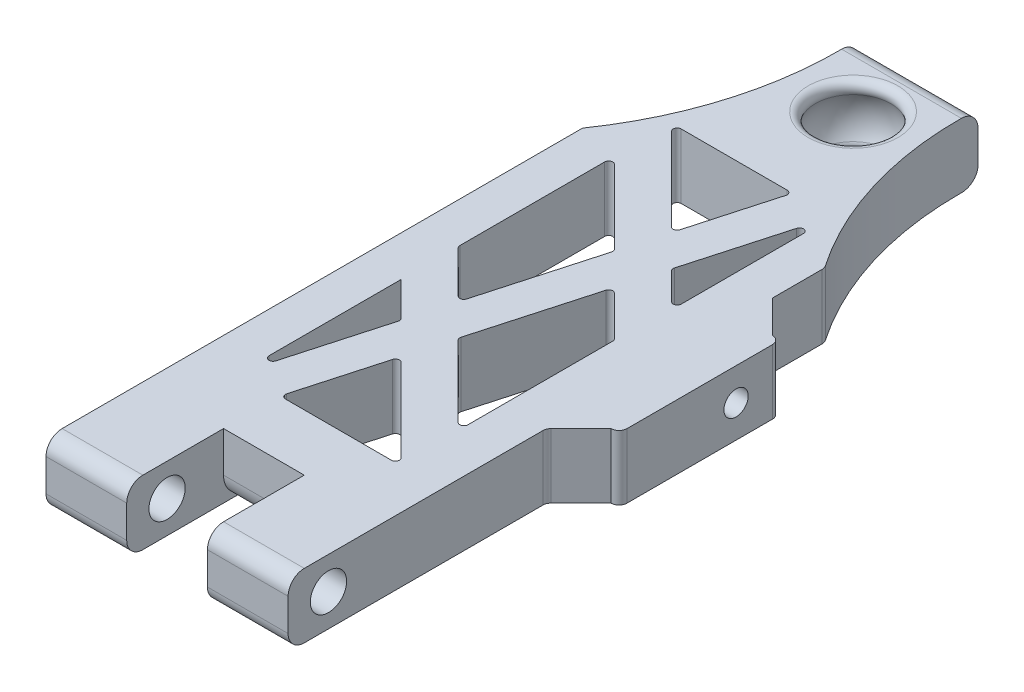
SolidWorks part; units mm, degrees
ref_plane "Front Plane" through (0, 0, 0) normal (0, 0, 1) x (1, 0, 0)
ref_plane "Top Plane" through (0, 0, 0) normal (0, 1, 0) x (1, 0, 0)
ref_plane "Right Plane" through (0, 0, 0) normal (1, 0, 0) x (0, 0, -1)
sketch "Sketch1" plane through (0, 0, 0) normal (0, 1, 0) x (1, 0, 0)
  line L1 (-15, 46.5) -> (15, 46.5)
  line L2 (-15, 46.5) -> (-15, -46.5)
  line L3 (-15, -46.5) -> (15, -46.5)
  line L4 (15, 46.5) -> (15, -46.5)
  line L5 (-15, 46.5) -> (15, -46.5) construction
  line L6 (-15, -46.5) -> (15, 46.5) construction
  point P0 (0, 0)
  dimension "D1" = 30
  dimension "D2" = 93
extrude "Boss-Extrude1" add sketch "Sketch1" along normal blind 8
sketch "Sketch2" plane through (0, 8, 0) normal (0, 1, 0) x (1, 0, 0)
  line L5 (-15, -46.5) -> (15, -46.5) construction
  line L6 (5, -46.5) -> (-5, -46.5)
  line L7 (5, -46.5) -> (5, -34.5)
  line L8 (5, -34.5) -> (-5, -34.5)
  line L9 (-5, -46.5) -> (-5, -34.5)
  line L10 (15, -46.5) -> (15, 46.5) construction
  dimension "D1" = 10
  dimension "D5" = 12
  dimension "D6" = 10
extrude "Cut-Extrude1" cut sketch "Sketch2" against normal blind 8
sketch "Sketch3" plane through (15, 0, 0) normal (1, 0, 0) x (0, 0, -1)
  line L0 (-46.5, 8) -> (-46.5, 0) construction
  line L1 (-46.5, 8) -> (46.5, 8) construction
  circle A0 centre (-41.5, 4) radius 2.25
  dimension "D1" = 4.5
  dimension "D2" = 5
  dimension "D3" = 4
extrude "Cut-Extrude2" cut sketch "Sketch3" against normal through all
fillet "Fillet1" radius 2 6 edges at (0, 0, -46.5) (0, 8, -46.5) (-10, 8, 46.5) (-10, 0, 46.5) (10, 0, 46.5) (10, 8, 46.5)
sketch "Sketch4" plane through (0, 8, 0) normal (0, 1, 0) x (1, 0, 0)
  line L0 (5, 26) -> (-10, 26)
  line L1 (-10, 26) -> (1.7153, 14.2847)
  line L2 (10, 6) -> (10, 26)
  line L3 (-10, -7.5) -> (-10, -27.5)
  line L4 (-5, -27.5) -> (10, -27.5)
  line L5 (10, -27.5) -> (-1.7153, -15.7847)
  line L6 (15, -44.5) -> (15, 44.5) construction
  line L7 (-15, 44.5) -> (-15, -44.5) construction
  line L8 (-10, 18.9289) -> (-10, -0.4289)
  line L9 (-10, -0.4289) -> (-4.072, -6.3569)
  line L10 (9.7326, -20.1615) -> (9.7326, -0.8036)
  line L11 (9.7326, -0.8036) -> (4.072, 4.8569)
  line L13 (5, -34.5) -> (-5, -34.5) construction
  line L14 (5, 26) -> (1.7153, 14.2847)
  line L15 (-5, -27.5) -> (-1.7153, -15.7847)
  line L16 (-0.1669, -10.262) -> (4.072, 4.8569)
  line L18 (5.6204, 10.3796) -> (10, 6)
  line L19 (0.1669, 8.762) -> (-10, 18.9289)
  line L20 (-0.1669, -10.262) -> (9.7326, -20.1615)
  line L21 (-5.6204, -11.8796) -> (-10, -7.5)
  line L22 (-5.6204, -11.8796) -> (-10, -27.5)
  line L23 (0.1669, 8.762) -> (-4.072, -6.3569)
  line L24 (5.6204, 10.3796) -> (10, 26)
  dimension "D1" = 5
  dimension "D2" = 5
  dimension "D3" = 5
  dimension "D4" = 45
  dimension "D5" = 45
  dimension "D6" = 5
  dimension "D7" = 5
  dimension "D9" = 7
  dimension "D10" = 20
  dimension "D11" = 20
  dimension "D12" = 15
  dimension "D13" = 14
extrude "Cut-Extrude3" cut sketch "Sketch4" against normal through all
fillet "Fillet2" radius 3 1 edges at (0, 0, 34.5)
sketch "Sketch5" plane through (0, 0, 0) normal (1, 0, 0) x (0, 0, -1)
  line L12 (38.5, 8) -> (38.5, 0)
  line L13 (-44.5, 8) -> (44.5, 8) construction
  line L14 (-44.5, 0) -> (44.5, 0) construction
  line L15 (38.5, 0) -> (42, 0)
  line L16 (42, 8) -> (38.5, 8)
  arc A4 (42, 0) -> (42, 8) centre (38.5, 4) ccw
  dimension "D1" = 38.5
  dimension "D2" = 3.5
sketch "Sketch6" plane through (0, 8, 0) normal (0, 1, 0) x (1, 0, 0)
  line L0 (-15, 46.5) -> (15, 46.5) construction
  line L1 (-15, 44.5) -> (-15, -44.5) construction
  line L2 (-7.4775, 46.5) -> (-15, 46.5)
  line L3 (-15, 46.5) -> (-15, 19.9832)
  line L4 (0, -55) -> (0, 55) construction
  line L5 (15, 46.5) -> (15, 19.9832)
  line L6 (7.4775, 46.5) -> (15, 46.5)
  arc A0 (-7.4775, 46.5) -> (-15, 19.9832) centre (-49.7917, 44.1785) cw
  arc A1 (7.4775, 46.5) -> (15, 19.9832) centre (49.7917, 44.1785) ccw
extrude "Cut-Extrude4" cut sketch "Sketch6" against normal through all both and the other way through all
revolve "Cut-Revolve1" cut sketch "Sketch5" angle 360 about L12
fillet "Fillet3" radius 1 2 edges at (0, 0, -35) (0, 8, -35)
fillet "Fillet4" radius 0.5 19 edges at (5, 4, -26) (-10, 4, -26) (1.7153, 4, -14.2847) (10, 4, -6) (5.6204, 4, -10.3796) (10, 4, -26) (-10, 4, -18.9289) (-10, 4, 0.4289) (-4.072, 4, 6.3569) (0.1669, 4, -8.762) (4.072, 4, -4.8569) (9.7326, 4, 0.8036) (-0.1669, 4, 10.262) (9.7326, 4, 20.1615) (-5.6204, 4, 11.8796) (-1.7153, 4, 15.7847) (10, 4, 27.5) (-5, 4, 27.5) (-10, 4, 27.5)
sketch "Sketch8" plane through (15, 0, 0) normal (1, 0, 0) x (0, 0, -1)
  line L0 (-44.5, 0) -> (19.9832, 0) construction
  line L1 (9.5, 0) -> (-10.5, 0)
  line L2 (9.5, 0) -> (9.5, 8)
  line L3 (9.5, 8) -> (-10.5, 8)
  line L4 (-10.5, 0) -> (-10.5, 8)
  line L5 (-44.5, 8) -> (19.9832, 8) construction
  line L6 (-46.5, 6) -> (-46.5, 2) construction
  dimension "D1" = 36
  dimension "D2" = 20
extrude "Boss-Extrude2" add sketch "Sketch8" along normal blind 5
sketch "Sketch9" plane through (20, 0, 0) normal (1, 0, 0) x (0, 0, -1)
  line L0 (9.5, 8) -> (-10.5, 8) construction
  circle A0 centre (4, 4) radius 1.5027
  dimension "D1" = 4
extrude "Cut-Extrude5" cut sketch "Sketch9" against normal blind 5 and the other way through all
chamfer "Chamfer1" distance 4 angle 45 2 edges at (15, 4, 10.5) (15, 4, -9.5)
fillet "Fillet5" radius 1 4 edges at (20, 4, 10.5) (15, 4, 14.5) (20, 4, -9.5)
